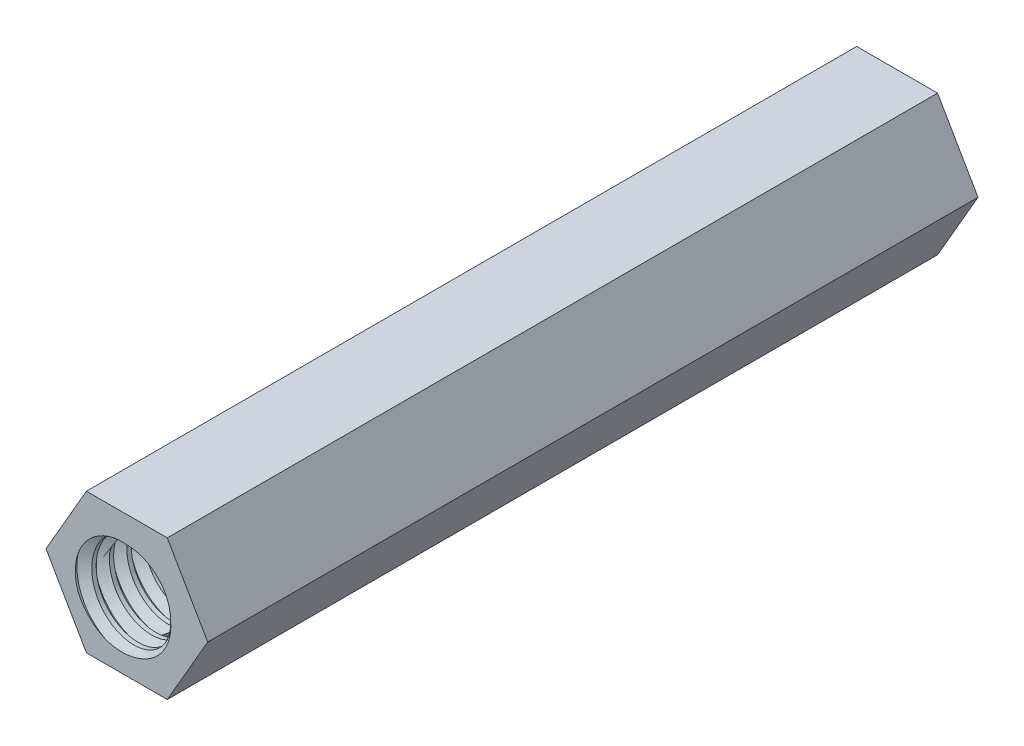
SolidWorks part; units mm, degrees
ref_plane "Front Plane" through (0, 0, 0) normal (0, 0, 1) x (1, 0, 0)
ref_plane "Top Plane" through (0, 0, 0) normal (0, 1, 0) x (1, 0, 0)
ref_plane "Right Plane" through (0, 0, 0) normal (1, 0, 0) x (0, 0, -1)
sketch "Sketch1" plane through (0, 0, 0) normal (0, 0, 1) x (1, 0, 0)
  line L1 (2.3094, 0) -> (1.1547, 2)
  line L2 (1.1547, 2) -> (-1.1547, 2)
  line L3 (-1.1547, 2) -> (-2.3094, 0)
  line L4 (-2.3094, 0) -> (-1.1547, -2)
  line L5 (-1.1547, -2) -> (1.1547, -2)
  line L6 (1.1547, -2) -> (2.3094, 0)
  circle A0 centre (0, 0) radius 2 construction
  dimension "D1" = 4
extrude "Boss-Extrude1" add sketch "Sketch1" against normal blind 22
sketch "Sketch2" plane through (0, 0, 0) normal (0, 0, 1) x (1, 0, 0)
  circle A0 centre (0, 0) radius 1.25
  dimension "D1" = 2.5
extrude "Cut-Extrude1" cut sketch "Sketch2" along normal through all and the other way through all
thread "Thread_M3x0.5_Internal_Through_RH" pitch 0.5 method cut profile "Thread Profile1" start angle 0, offset 0, length 0, pitch 0.5, diameter 2.5
ref_plane "Plane1" through (1.25, 0, -22) normal (0, -1, 0) x (1, 0, 0)
sketch "Thread Profile1" plane through (1.25, 0, -22) normal (0, -1, 0) x (1, 0, 0)
  line L0 (0, 0) -> (0, 0.5) construction
  line L1 (0, 0) -> (0.2706, 0.1562)
  line L2 (0.2706, 0.1562) -> (0.2706, 0.2187)
  line L3 (0.2706, 0.2187) -> (0, 0.375)
  line L4 (0.2706, 0.1875) -> (0, 0.1875) construction
  line L11 (0, 0) -> (0, 0.375)
  point P2 (0, 0)
  dimension "Pitch" = 0.5
  dimension "Profile_Angle" = 60
  dimension "Profile_Land" = 0.0625
  dimension "Profile_Height" = 0.2706
